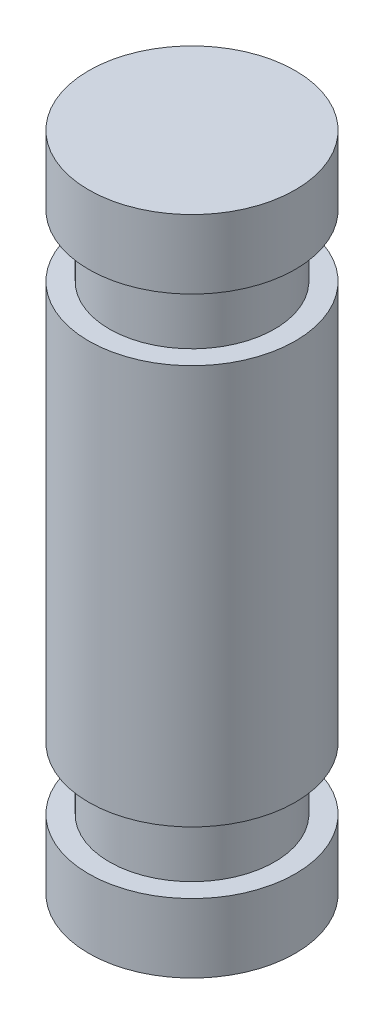
SolidWorks part; units mm, degrees
material "Plain Carbon Steel"
ref_plane "XY" through (0, 0, 0) normal (1, 0, 0) x (0, 1, 0)
ref_plane "XZ" through (0, 0, 0) normal (0, 0, 1) x (0, 1, 0)
ref_plane "YZ" through (0, 0, 0) normal (0, 1, 0) x (-1, 0, 0)
sketch "Sketch1" plane through (0, 0, 0) normal (1, 0, 0) x (0, 1, 0)
  line L0 (0, 0) -> (4.8, 0)
  line L1 (55, 0) -> (-55, 0) construction
  line L2 (4.8, 0) -> (4.8, 1.5)
  line L3 (4.8, 1.5) -> (3.8, 1.5)
  line L4 (-2.9, 1.5) -> (-2.9, 1.2)
  line L5 (-2.9, 1.2) -> (-3.8, 1.2)
  line L7 (-3.8, 1.2) -> (-3.8, 1.5)
  line L8 (-3.8, 1.5) -> (-4.8, 1.5)
  line L9 (-4.8, 1.5) -> (-4.8, 0)
  line L10 (-4.8, 0) -> (0, 0)
  line L11 (4.8, 0) -> (51.7835, 0) construction
  line L12 (2.9, 1.5) -> (2.9, 1.2)
  line L13 (2.9, 1.2) -> (3.8, 1.2)
  line L14 (3.8, 1.2) -> (3.8, 1.5)
  line L15 (2.9, 1.5) -> (-2.9, 1.5)
  point P23 (0, 1.5)
  dimension "D1" = 1
  dimension "D2" = 3
  dimension "D3" = 0.9
  dimension "D6" = 0.9
  dimension "D7" = 5.8
  dimension "D8" = 2.4
revolve "Revolve1" add sketch "Sketch1" angle 360 about L11
